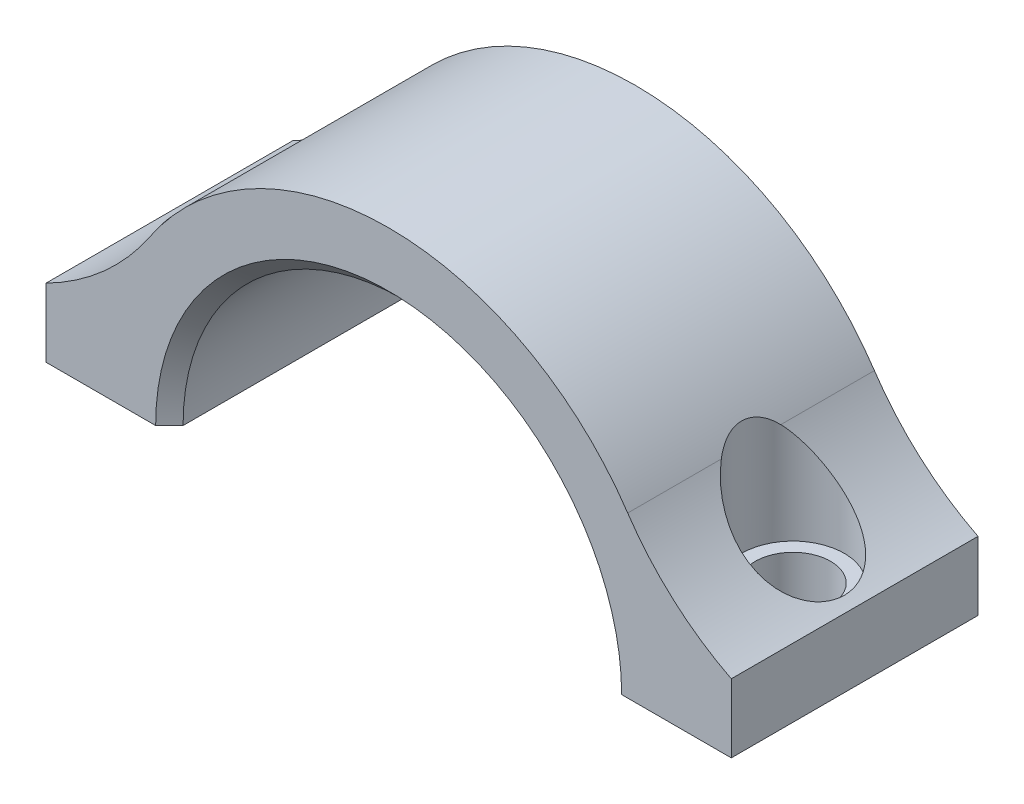
SolidWorks part; units mm, degrees
ref_plane "Alzado" through (0, 0, 0) normal (0, 0, 1) x (1, 0, 0)
ref_plane "Planta" through (0, 0, 0) normal (0, 1, 0) x (1, 0, 0)
ref_plane "Vista lateral" through (0, 0, 0) normal (1, 0, 0) x (0, 0, -1)
sketch "Croquis1" plane through (0, 0, 0) normal (0, 0, 1) x (1, 0, 0)
  line L0 (32, 0) -> (50, 0)
  line L1 (-32, 0) -> (-50, 0)
  line L2 (-50, 0) -> (-50, 10)
  line L3 (-50, 10) -> (-40.7922, 10)
  line L4 (50, 0) -> (50, 10)
  line L5 (50, 10) -> (40.7922, 10)
  arc A0 (32, 0) -> (-32, 0) centre (0, 0) ccw
  arc A1 (40.7922, 10) -> (-40.7922, 10) centre (0, 0) ccw
  dimension "D1" = 64
  dimension "D3" = 10
  dimension "D2" = 18
  dimension "D4" = 18
  dimension "D5" = 10
  dimension "D6" = 10
extrude "Saliente-Extruir1" add sketch "Croquis1" along normal blind 36
ref_plane "Plano1" through (0, 10, 0) normal (0, 1, 0) x (1, 0, 0)
sketch "Croquis2" plane through (0, 10, 0) normal (0, 1, 0) x (1, 0, 0)
  line L0 (32, -36) -> (50, -36) construction
  line L1 (32, -36) -> (50, -36) construction
  line L2 (32, -36) -> (50, 0) construction
  circle A0 centre (41, -18) radius 7.5
  point P2 (41, -18)
  dimension "D1" = 15
extrude "Cortar-Extruir1" cut sketch "Croquis2" along normal blind 36
mirror "Simetría1" about plane through (0, 0, 0) normal (1, 0, 0) of "Cortar-Extruir1"
sketch "Croquis3" plane through (0, 10, 0) normal (0, 1, 0) x (1, 0, 0)
  line L0 (-32, -36) -> (-50, 0) construction
  line L2 (-40.7922, -36) -> (-50, -36) construction
  point P3 (-45.4943, -70.1255)
  point P8 (-41, -18)
hole_wizard "Refrentado para perno con cabeza hexagonal (calidades AB) de M21" positions "Croquis3D1" profile "Croquis4" counterbore size "M2" standard "AS"
sketch3d "Croquis3D1"
  point P0 (-41, 10, 18)
  point P3 (41, 10, 18)
sketch "Croquis4" plane through (-41, 10, 18) normal (1, 0, 0) x (0, 0, 1)
  line L0 (0, 0) -> (0, 43.3047)
  line L1 (0, 43.3047) -> (5.5, 40)
  line L2 (5.5, 40) -> (5.5, 1.4)
  line L3 (5.5, 1.4) -> (7.5, 1.4)
  line L4 (7.5, 1.4) -> (7.5, 0)
  line L5 (7.5, 0) -> (0, 0)
  line L10 (0, 43.3047) -> (-5.5, 40) construction
  line L11 (0, -6.35) -> (0, 107.95) construction
  dimension "Diámetro de taladro" = 11
  dimension "Profundidad de taladro" = 40
  dimension "Diámetro de refrentado" = 15
  dimension "Profundidad de refrentado" = 1.4
  dimension "Ángulo de perforador" = 118
fillet "Redondeo1" radius 40 2 edges at (40.7922, 10, 30.7486) (-40.7922, 10, 5.2514)
chamfer "Chaflán1" distance 2 angle 45 2 edges at (0, 32, 0) (0, 32, 36)
